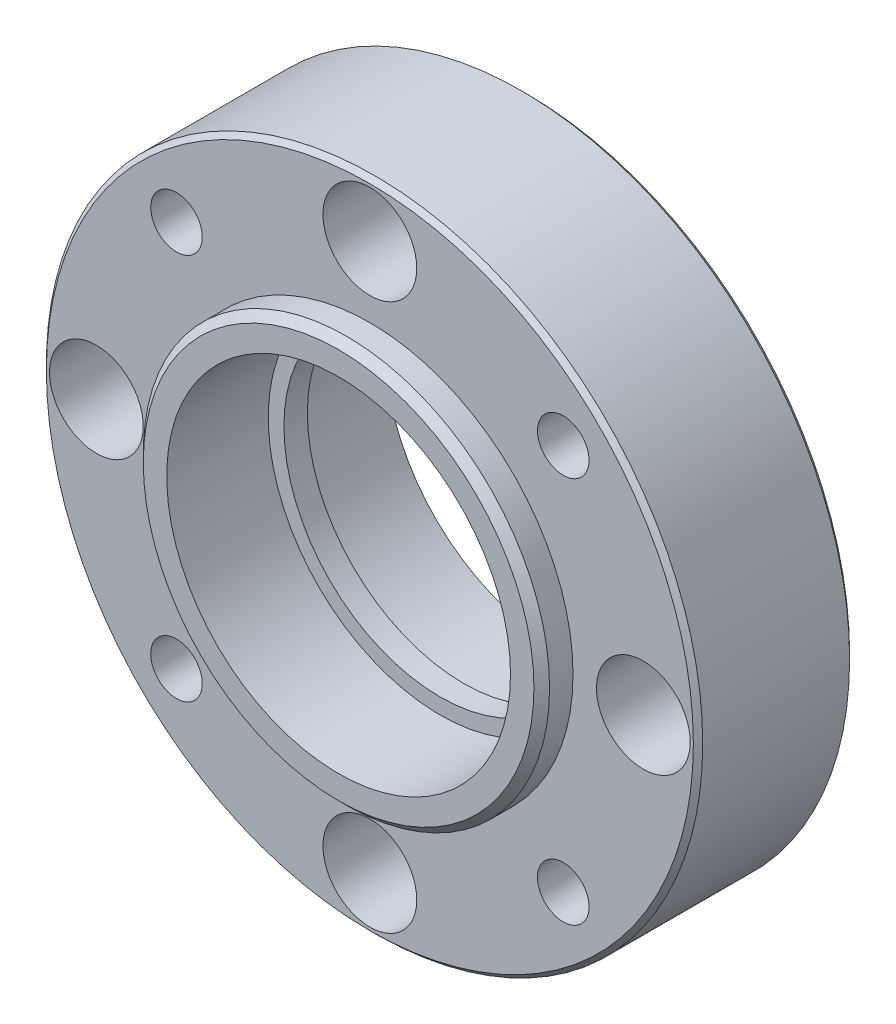
SolidWorks part; units mm, degrees
material "6061 合金"
ref_plane "前视基准面" through (0, 0, 0) normal (0, 0, 1) x (1, 0, 0)
ref_plane "上视基准面" through (0, 0, 0) normal (0, 1, 0) x (1, 0, 0)
ref_plane "右视基准面" through (0, 0, 0) normal (1, 0, 0) x (0, 0, -1)
sketch "草图1" plane through (0, 0, 0) normal (0, 1, 0) x (1, 0, 0)
  line L0 (21, 5) -> (0, 5)
  line L1 (0, 5) -> (0, -5)
  line L2 (0, -5) -> (21, -5)
  line L3 (21, -5) -> (21, 5)
  line L4 (0, 5) -> (0, -5) construction
revolve "旋转1" add sketch "草图1" angle 360 about L4 reverse direction yes
sketch "草图2" plane through (0, 0, -5) normal (0, 0, -1) x (-1, 0, 0)
  circle A0 centre (0, 0) radius 13.4
extrude "凸台-拉伸1" add sketch "草图2" along normal blind 2
sketch "草图3" plane through (0, 0, 5) normal (0, 0, 1) x (1, 0, 0)
  circle A0 centre (0, 0) radius 13
extrude "凸台-拉伸2" add sketch "草图3" along normal blind 2
sketch "草图4" plane through (0, 0, 0) normal (0, 1, 0) x (1, 0, 0)
  line L0 (11, 7) -> (0, 7)
  line L1 (0, 7) -> (0, -7)
  line L2 (0, -7) -> (11, -7)
  line L3 (11, -7) -> (11, -0.5)
  line L4 (11, -0.5) -> (10, -0.5)
  line L5 (10, -0.5) -> (10, 1)
  line L6 (10, 1) -> (11, 1)
  line L7 (11, 1) -> (11, 7)
  line L8 (0, 7) -> (0, -7) construction
revolve "切除-旋转1" cut sketch "草图4" angle 360 about L8 reverse direction yes
hole_wizard "M3 六角头机械螺钉的柱形沉头孔1" positions "草图6" profile "草图5" counterbore size "M3" standard "ANSI Metric"
sketch "草图6" plane through (0, 0, 5) normal (0, 0, 1) x (1, 0, 0)
  point P0 (0, 17.5)
  point P1 (17.5, 0)
  point P2 (0, -17.5)
  point P3 (-17.5, 0)
sketch "草图5" plane through (0, 17.5, 5) normal (1, 0, 0) x (0, -1, 0)
  line L0 (0, 0) -> (0, 12)
  line L1 (0, 12) -> (1.75, 12)
  line L3 (1.75, 12) -> (1.75, 5)
  line L4 (1.75, 5) -> (3, 5)
  line L5 (3, 5) -> (3, 0)
  line L7 (3, 0) -> (0, 0)
  line L11 (0, -6.35) -> (0, 107.95) construction
  dimension "通孔孔直径" = 3.5
  dimension "通孔孔深度" = 12
  dimension "柱形沉头孔直径" = 6
  dimension "柱形沉头孔深度" = 5
hole_wizard "Ø3.3 (3.3) 直径孔1" positions "草图8" profile "草图7" hole size "Ø3.3" standard "ANSI Metric"
sketch "草图8" plane through (0, 0, -5) normal (0, 0, -1) x (-1, 0, 0)
  point P0 (12.3744, 12.3744)
  point P1 (-12.3744, 12.3744)
  point P2 (-12.3744, -12.3744)
  point P3 (12.3744, -12.3744)
sketch "草图7" plane through (-12.3744, 12.3744, -5) normal (1, 0, 0) x (0, 1, 0)
  line L0 (0, 0) -> (0, 12)
  line L1 (0, 12) -> (1.65, 12)
  line L2 (1.65, 12) -> (1.65, 0)
  line L5 (1.65, 0) -> (0, 0)
  line L11 (0, -6.35) -> (0, 107.95) construction
  dimension "通孔孔直径" = 3.3
  dimension "通孔孔深度" = 12
chamfer "倒角1" distance 0.3 angle 45 2 edges at (21, 0, -5) (21, 0, 5)
chamfer "倒角2" distance 0.5 angle 45 2 edges at (13, 0, 7) (-13.4, 0, -7)
